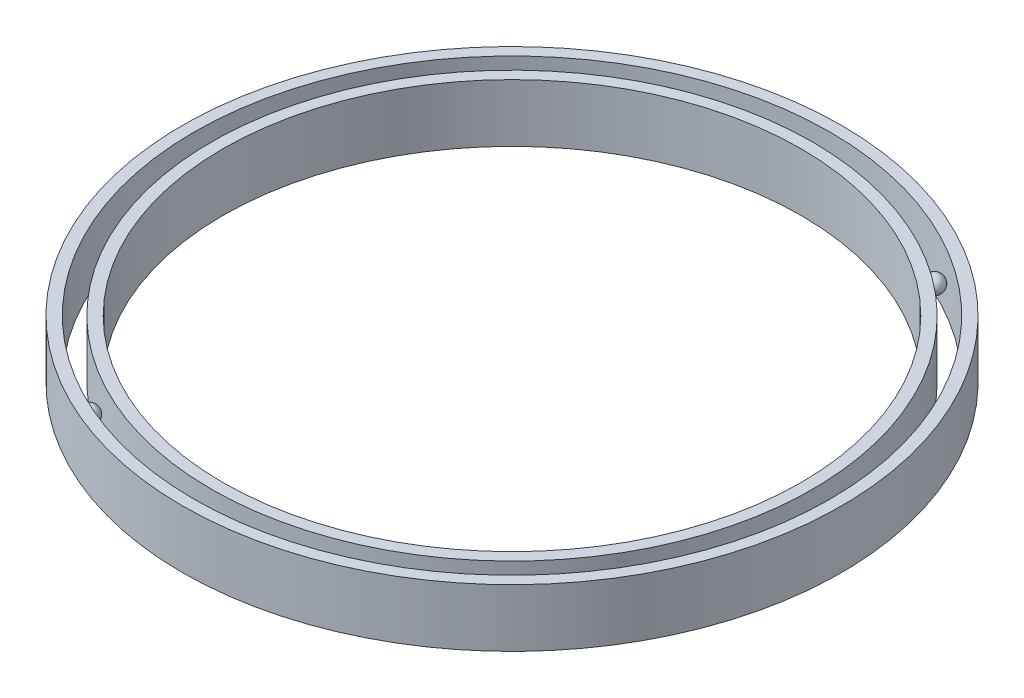
SolidWorks part; units mm, degrees
ref_plane "Front Plane" through (0, 0, 0) normal (0, 0, 1) x (1, 0, 0)
ref_plane "Top Plane" through (0, 0, 0) normal (0, 1, 0) x (1, 0, 0)
ref_plane "Right Plane" through (0, 0, 0) normal (1, 0, 0) x (0, 0, -1)
sketch "Sketch1" plane through (0, 0, 0) normal (0, 0, 1) x (1, 0, 0)
  line L0 (0, 0) -> (0, 98.0663) construction
  line L1 (100, 10) -> (100, -10)
  line L2 (100, 10) -> (104, 10)
  line L3 (100, -10) -> (104, -10)
  line L4 (104, 10) -> (104, -10)
  dimension "D1" = 100
  dimension "D2" = 4
  dimension "D3" = 20
  dimension "D4" = 10
revolve "Revolve1" add sketch "Sketch1" angle 360 about L0
sketch "Sketch2" plane through (0, 0, 0) normal (0, 0, 1) x (1, 0, 0)
  line L0 (110, 10) -> (110, -10)
  line L1 (110, 10) -> (114, 10)
  line L2 (110, -10) -> (114, -10)
  line L3 (114, 10) -> (114, -10)
  line L4 (0, 0) -> (0, 62.8699) construction
  point P4 (0, 0)
  dimension "D1" = 110
  dimension "D2" = 4
  dimension "D3" = 10
  dimension "D4" = 20
revolve "Revolve2" add sketch "Sketch2" angle 360 about L4
sketch "Sketch3" plane through (0, 0, 0) normal (0, 1, 0) x (1, 0, 0)
  line L0 (104, 0) -> (110, 0)
  line L1 (0, 0) -> (110, 0) construction
  circle A0 centre (0, 0) radius 104 construction
  circle A1 centre (0, 0) radius 110 construction
  arc A2 (110, 0) -> (104, 0) centre (107, 0) ccw
revolve "Revolve3" add sketch "Sketch3" angle 360 about L0
pattern_circular "CirPattern1" count 6 over 360 about axis through (0, 10, 0) along (0, -1, 0) of bodies 166
